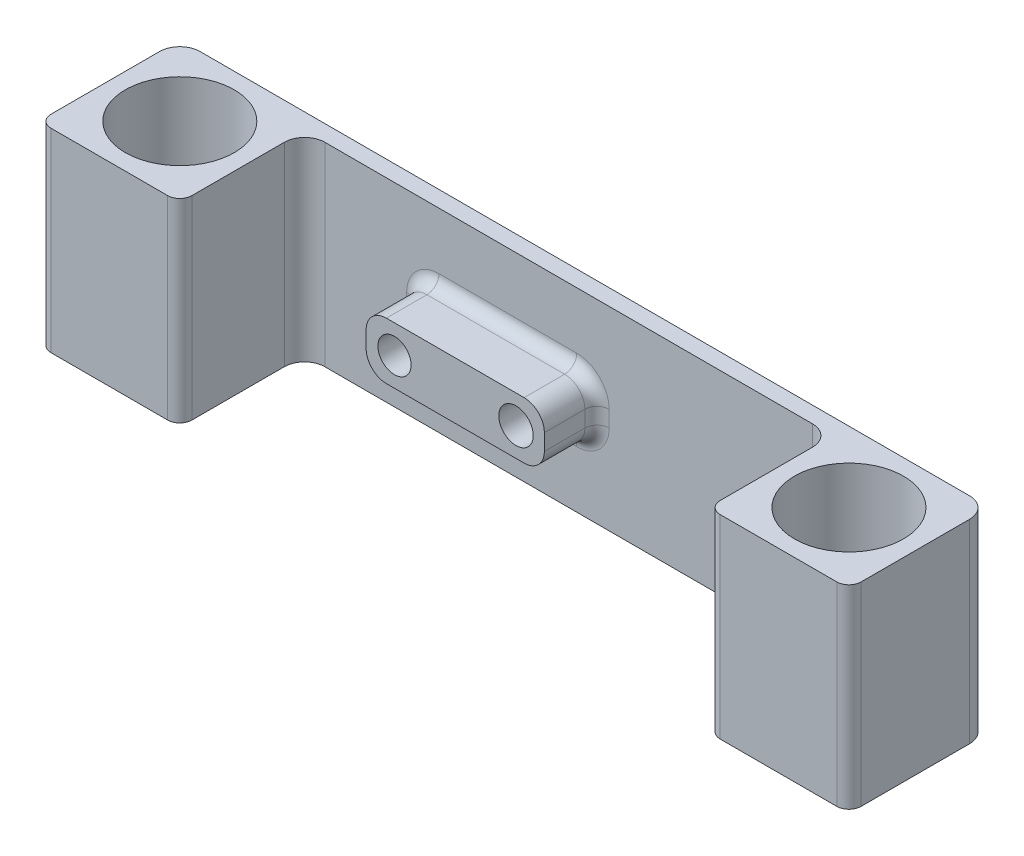
SolidWorks part; units mm, degrees
ref_plane "Front Plane" through (0, 0, 0) normal (0, 0, 1) x (1, 0, 0)
ref_plane "Top Plane" through (0, 0, 0) normal (0, 1, 0) x (1, 0, 0)
ref_plane "Right Plane" through (0, 0, 0) normal (1, 0, 0) x (0, 0, -1)
sketch "Sketch1" plane through (0, 0, 0) normal (0, 1, 0) x (1, 0, 0)
  line L1 (-17.4, 17.4) -> (17.4, 17.4)
  line L2 (-17.4, 13.4) -> (-17.4, -17.4)
  line L3 (-17.4, -17.4) -> (17.4, -17.4)
  line L4 (17.4, 17.4) -> (17.4, -17.4)
  line L5 (0, -17.4) -> (0, 17.4) construction
  line L6 (-17.4, 0) -> (17.4, 0) construction
  line L7 (-17.4, 17.4) -> (-82.6, 17.4)
  line L9 (-17.4, 13.4) -> (-82.6, 13.4)
  line L10 (-82.6, 17.4) -> (-82.6, 13.4)
  circle A0 centre (0, 0) radius 13.45
  dimension "D1" = 26.9
  dimension "D2" = 34.8
  dimension "D3" = 34.8
  dimension "D4" = 65.2
  dimension "D5" = 4
extrude "Boss-Extrude2" add sketch "Sketch1" along normal blind 48
mirror "Mirror2" about plane through (-82.6, 48, -17.4) normal (1, 0, 0) of "Boss-Extrude2"
sketch "Sketch7" plane through (0, 0, -13.4) normal (0, 0, 1) x (1, 0, 0)
  line L0 (-147.8, 24) -> (-17.4, 24) construction
  line L1 (-147.8, 48) -> (-147.8, 0) construction
  line L2 (-17.4, 48) -> (-17.4, 0) construction
  line L3 (-82.6, 48) -> (-82.6, 0) construction
  line L4 (-147.8, 48) -> (-17.4, 48) construction
  line L5 (-147.8, 0) -> (-17.4, 0) construction
  line L6 (-112.6, 24) -> (-82.6, 24) construction
  line L8 (-119.6, 17) -> (-75.6, 17)
  line L9 (-119.6, 17) -> (-119.6, 31)
  line L10 (-119.6, 31) -> (-75.6, 31)
  line L11 (-75.6, 17) -> (-75.6, 31)
  line L12 (-97.6, 31) -> (-97.6, 17) construction
  line L13 (-119.6, 24) -> (-75.6, 24) construction
  circle A0 centre (-82.6, 24) radius 4.25
  circle A2 centre (-112.6, 24) radius 4.1
  point P15 (-97.6, 24)
  dimension "D1" = 8.5
  dimension "D3" = 8.2
  dimension "D5" = 30
  dimension "D2" = 14
  dimension "D4" = 44
extrude "Boss-Extrude3" add sketch "Sketch7" along normal blind 13
fillet "Fillet1" radius 3 4 edges at (17.4, 24, 17.4) (-17.4, 24, 17.4) (-182.6, 24, 17.4) (-147.8, 24, 17.4)
fillet "Fillet2" radius 5 4 edges at (17.4, 24, -17.4) (-17.4, 24, -13.4) (-182.6, 24, -17.4) (-147.8, 24, -13.4)
fillet "Fillet3" radius 5 4 edges at (-75.6, 31, -6.9) (-75.6, 17, -6.9) (-119.6, 31, -6.9) (-119.6, 17, -6.9)
fillet "Fillet4" radius 3 8 edges at (-118.1355, 18.4645, -13.4) (-119.6, 24, -13.4) (-118.1355, 29.5355, -13.4) (-97.6, 31, -13.4) (-77.0645, 29.5355, -13.4) (-75.6, 24, -13.4) (-77.0645, 18.4645, -13.4) (-97.6, 17, -13.4)
sketch "Sketch8" plane through (0, 0, -13.4) normal (0, 0, 1) x (1, 0, 0)
  circle A0 centre (-112.6, 24) radius 4.1 construction
  circle A1 centre (-82.6, 24) radius 4.25 construction
  circle A2 centre (-112.6, 24) radius 4.1
  circle A3 centre (-82.6, 24) radius 4.25
extrude "Cut-Extrude1" cut sketch "Sketch8" against normal through all
